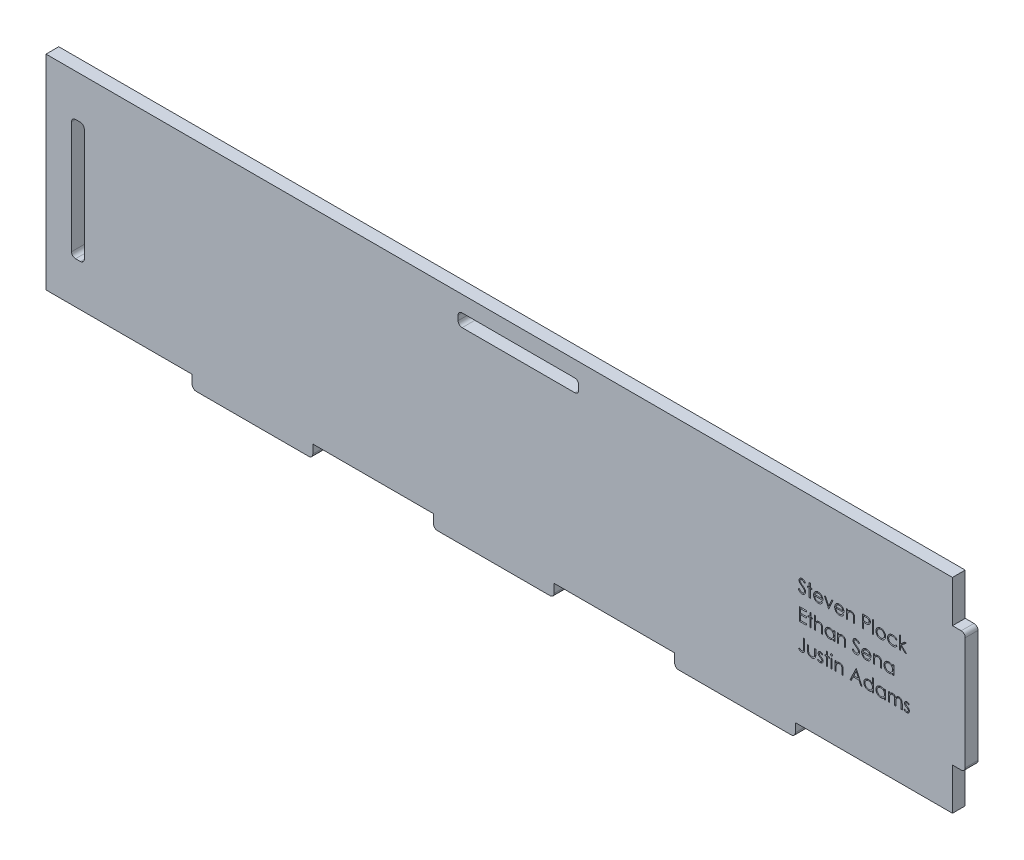
SolidWorks part; units mm, degrees
ref_plane "Front Plane" through (0, 0, 0) normal (0, 0, 1) x (1, 0, 0)
ref_plane "Top Plane" through (0, 0, 0) normal (0, 1, 0) x (1, 0, 0)
ref_plane "Right Plane" through (0, 0, 0) normal (1, 0, 0) x (0, 0, -1)
sketch "Sketch1" plane through (0, 0, 0) normal (0, 0, 1) x (1, 0, 0)
  line L1 (-112.715, -25.4) -> (112.715, -25.4)
  line L2 (-112.715, -25.4) -> (-112.715, 25.4)
  line L3 (-112.715, 25.4) -> (112.715, 25.4)
  line L4 (112.715, -25.4) -> (112.715, 25.4)
  line L5 (-112.715, -25.4) -> (112.715, 25.4) construction
  line L6 (-112.715, 25.4) -> (112.715, -25.4) construction
  point P0 (0, 0)
  dimension "D1" = 50.8
  dimension "D2" = 225.43
extrude "Boss-Extrude1" add sketch "Sketch1" along normal blind 3.175
sketch "Sketch2" plane through (0, 0, 3.175) normal (0, 0, 1) x (1, 0, 0)
  line L0 (-112.715, 0) -> (-106.365, 0) construction
  line L1 (-112.715, 25.4) -> (-112.715, -25.4) construction
  line L3 (-106.365, 15) -> (-103.19, 15)
  line L4 (-103.19, 15) -> (-103.19, -15)
  line L5 (-103.19, -15) -> (-106.365, -15)
  line L7 (-106.365, 15) -> (-106.365, -15)
  point P9 (-106.365, 0)
  dimension "D1" = 6.35
  dimension "D2" = 30
extrude "Cut-Extrude1" cut sketch "Sketch2" against normal blind 10
ref_plane "Plane1" through (112.715, 25.4, 0) normal (0, 1, 0) x (1, 0, 0)
sketch "Sketch4" plane through (112.715, 0, 0) normal (1, 0, 0) x (0, 0, -1)
  line L0 (0, 0) -> (-3.175, 0) construction
  line L1 (-3.175, -25.4) -> (-3.175, 25.4) construction
  line L2 (0, -25.4) -> (0, 25.4) construction
  line L3 (-3.175, -15) -> (0, -15)
  line L4 (-3.175, -15) -> (-3.175, 15)
  line L5 (-3.175, 15) -> (0, 15)
  line L6 (0, -15) -> (0, 15)
  line L7 (-3.175, -15) -> (0, 15) construction
  line L8 (-3.175, 15) -> (0, -15) construction
  point P5 (-1.5875, 0)
  dimension "D1" = 30
extrude "Boss-Extrude2" add sketch "Sketch4" along normal blind 3.175
sketch "Sketch5" plane through (0, -25.4, 0) normal (0, -1, 0) x (1, 0, 0)
  line L0 (-112.715, 1.5875) -> (-46.365, 1.5875) construction
  line L1 (-112.715, 3.175) -> (-112.715, 0) construction
  line L2 (-112.715, 3.175) -> (112.715, 3.175) construction
  line L3 (-46.365, 3.175) -> (-76.365, 3.175)
  line L4 (-46.365, 3.175) -> (-46.365, 0)
  line L5 (-46.365, 0) -> (-76.365, 0)
  line L6 (-76.365, 3.175) -> (-76.365, 0)
  line L7 (-112.715, 0) -> (112.715, 0) construction
  line L8 (13.635, 3.175) -> (13.635, 0)
  line L9 (13.635, 3.175) -> (-16.365, 3.175)
  line L10 (-16.365, 3.175) -> (-16.365, 0)
  line L11 (13.635, 0) -> (-16.365, 0)
  line L12 (73.635, 3.175) -> (73.635, 0)
  line L13 (73.635, 3.175) -> (43.635, 3.175)
  line L14 (43.635, 3.175) -> (43.635, 0)
  line L15 (73.635, 0) -> (43.635, 0)
  line L16 (-46.365, 3.175) -> (13.635, 3.175) construction
  point P12 (-76.365, 1.5875)
  dimension "D1" = 36.35
  dimension "D2" = 30
  dimension "D4" = 60
  dimension "D3" = 3
extrude "Boss-Extrude3" add sketch "Sketch5" along normal blind 3.175
sketch "Sketch6" plane through (0, 0, 3.175) normal (0, 0, 1) x (1, 0, 0)
  line L1 (112.715, 25.4) -> (-112.715, 25.4) construction
  line L2 (19.77, 19.8125) -> (112.715, 20.2) construction
  line L3 (-10.23, 18.225) -> (19.77, 18.225)
  line L4 (-10.23, 18.225) -> (-10.23, 21.4)
  line L5 (-10.23, 21.4) -> (19.77, 21.4)
  line L6 (19.77, 18.225) -> (19.77, 21.4)
  line L7 (-10.23, 18.225) -> (19.77, 21.4) construction
  line L8 (-10.23, 21.4) -> (19.77, 18.225) construction
  line L9 (112.715, 15) -> (112.715, 25.4) construction
  dimension "D1" = 3.175
  dimension "D2" = 30
  dimension "D3" = 4
  dimension "D4" = 92.945
extrude "Cut-Extrude2" cut sketch "Sketch6" against normal blind 10
fillet "Fillet1" radius 1 16 edges at (115.89, -15, 1.5875) (115.89, 15, 1.5875) (73.635, -28.575, 1.5875) (-76.365, -28.575, 1.5875) (-46.365, -28.575, 1.5875) (-16.365, -28.575, 1.5875) (43.635, -28.575, 1.5875) (13.635, -28.575, 1.5875) (-10.23, 21.4, 1.5875) (-10.23, 18.225, 1.5875) (19.77, 18.225, 1.5875) (19.77, 21.4, 1.5875) (-103.19, 15, 1.5875) (-106.365, 15, 1.5875) (-106.365, -15, 1.5875) (-103.19, -15, 1.5875)
sketch "Sketch7" plane through (0, 0, 3.175) normal (0, 0, 1) x (1, 0, 0)
  text T0 "Steven Plock\r\nEthan Sena\r\nJustin Adams"
extrude "Cut-Extrude3" cut sketch "Sketch7" against normal blind 2
